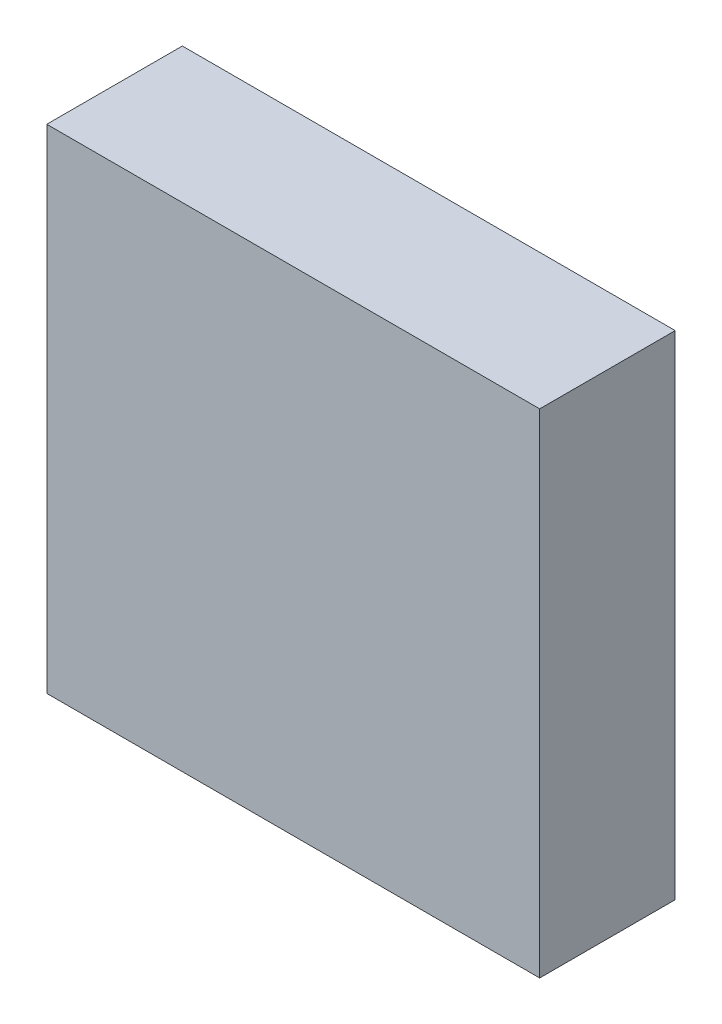
SolidWorks part; units mm, degrees
material "Custom Plastic"
ref_plane "Front Plane" through (0, 0, 0) normal (0, 0, 1) x (1, 0, 0)
ref_plane "Top Plane" through (0, 0, 0) normal (0, 1, 0) x (1, 0, 0)
ref_plane "Right Plane" through (0, 0, 0) normal (1, 0, 0) x (0, 0, -1)
other "Configuration Table"
sketch "Sketch1" plane through (0, 0, 0) normal (0, 0, 1) x (1, 0, 0)
  circle A0 centre (0, 0) radius 150
  dimension "D1" = 300
extrude "Boss-Extrude1" add sketch "Sketch1" along normal mid plane 50
sketch "Sketch2" plane through (0, 0, 0) normal (0, 0, 1) x (1, 0, 0)
  line L1 (-200, -200) -> (200, -200)
  line L2 (-200, -200) -> (-200, 200)
  line L3 (-200, 200) -> (200, 200)
  line L4 (200, -200) -> (200, 200)
  line L5 (-200, -200) -> (200, 200) construction
  line L6 (-200, 200) -> (200, -200) construction
  circle A0 centre (0, 0) radius 160
  dimension "D1" = 320
  dimension "D2" = 400
extrude "Boss-Extrude2" add sketch "Sketch2" along normal mid plane 60 separate body
sketch "Sketch3" plane through (0, 0, 30) normal (0, 0, 1) x (1, 0, 0)
  line L4 (200, -200) -> (200, 200)
  line L5 (200, 200) -> (-200, 200)
  line L6 (-200, 200) -> (-200, -200)
  line L7 (-200, -200) -> (200, -200)
  line L8 (200, -200) -> (200, 200)
  line L9 (200, 200) -> (-200, 200)
  line L10 (-200, 200) -> (-200, -200)
  line L11 (-200, -200) -> (200, -200)
  dimension "D1" = 0
extrude "Boss-Extrude3" add sketch "Sketch3" along normal blind 25
mirror "Mirror1" about plane through (0, 0, 0) normal (0, 0, 1) of "Boss-Extrude3"
